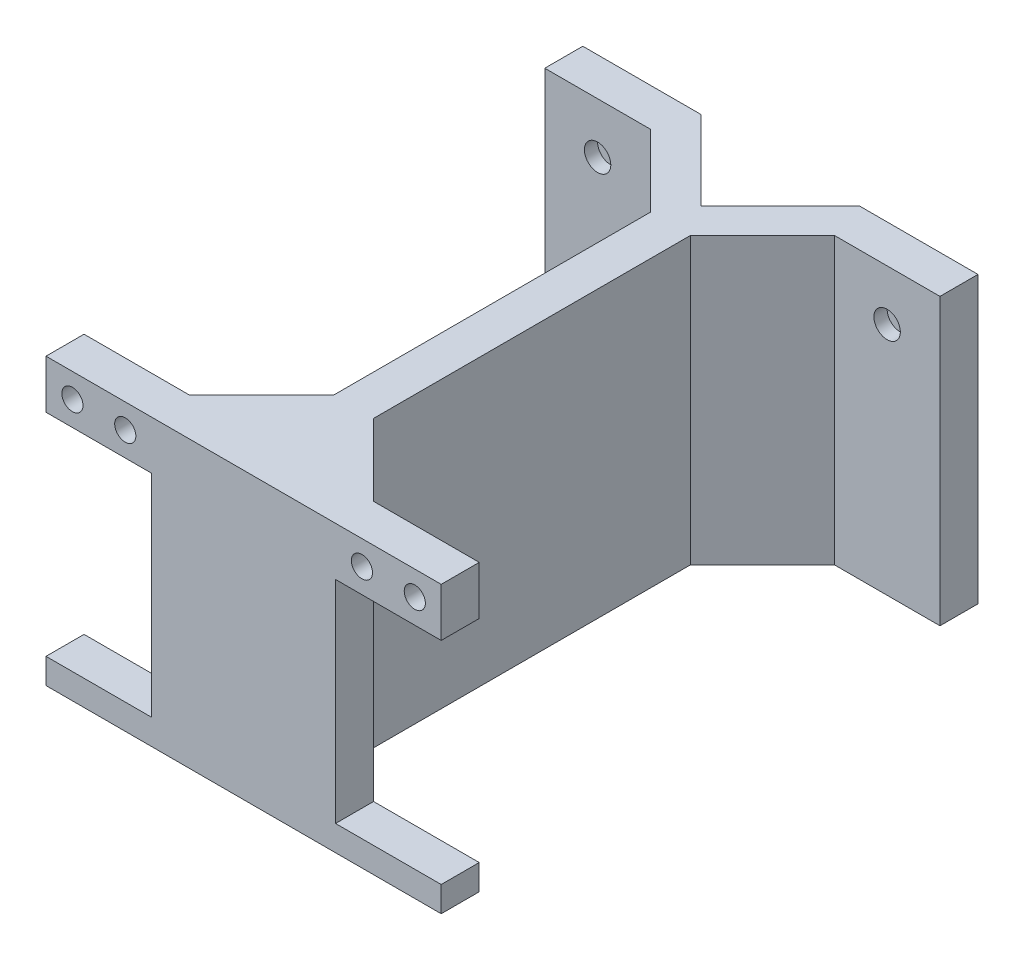
SolidWorks part; units mm, degrees
ref_plane "Front Plane" through (0, 0, 0) normal (0, 0, 1) x (1, 0, 0)
ref_plane "Top Plane" through (0, 0, 0) normal (0, 1, 0) x (1, 0, 0)
ref_plane "Right Plane" through (0, 0, 0) normal (1, 0, 0) x (0, 0, -1)
sketch "Sketch2" plane through (0, 0, 0) normal (0, 0, 1) x (1, 0, 0)
  line L1 (-40.6077, 18.1865) -> (34.1923, 18.1865)
  line L2 (-40.6077, 18.1865) -> (-40.6077, -35.8135)
  line L3 (-40.6077, -35.8135) -> (34.1923, -35.8135)
  line L4 (34.1923, 18.1865) -> (34.1923, -35.8135)
  dimension "D1" = 74.8
  dimension "D2" = 54
extrude "Boss-Extrude1" add sketch "Sketch2" along normal blind 101.6
sketch "Sketch3" plane through (0, 18.1865, 0) normal (0, 1, 0) x (1, 0, 0)
  line L0 (-40.6077, -7.2) -> (-20.6077, -7.2)
  line L1 (-40.6077, -101.6) -> (-40.6077, 0) construction
  line L2 (-20.6077, -7.2) -> (-7.0077, -20.8)
  line L3 (-7.0077, -20.8) -> (-7.0077, -80.8)
  line L4 (-7.0077, -80.8) -> (-20.6077, -94.4)
  line L5 (-20.6077, -94.4) -> (-40.6077, -94.4)
  line L6 (-40.6077, -94.4) -> (-40.6077, -7.2)
  line L7 (34.1923, -101.6) -> (-40.6077, -101.6) construction
  line L8 (34.1923, 0) -> (-40.6077, 0) construction
  dimension "D1" = 7.2
  dimension "D2" = 7.2
  dimension "D3" = 20
  dimension "D4" = 20
  dimension "D5" = 135
  dimension "D6" = 60
extrude "Cut-Extrude1" cut sketch "Sketch3" against normal blind 101.6
sketch "Sketch4" plane through (0, 18.1865, 0) normal (0, 1, 0) x (1, 0, 0)
  line L0 (34.1923, -94.4) -> (14.1923, -94.4)
  line L1 (34.1923, -101.6) -> (34.1923, 0) construction
  line L2 (14.1923, -94.4) -> (0.5923, -80.8)
  line L3 (0.5923, -80.8) -> (0.5923, -20.8)
  line L4 (0.5923, -20.8) -> (14.1923, -7.2)
  line L5 (14.1923, -7.2) -> (34.1923, -7.2)
  line L6 (34.1923, -7.2) -> (34.1923, -94.4)
  line L7 (34.1923, -101.6) -> (-40.6077, -101.6) construction
  line L8 (34.1923, 0) -> (-40.6077, 0) construction
  dimension "D1" = 7.2
  dimension "D2" = 7.2
  dimension "D3" = 20
  dimension "D4" = 20
  dimension "D5" = 135
  dimension "D6" = 135
  dimension "D7" = 60
extrude "Cut-Extrude2" cut sketch "Sketch4" against normal blind 101.6
sketch "Sketch5" plane through (0, 0, 101.6) normal (0, 0, 1) x (1, 0, 0)
  line L0 (34.1923, -35.8135) -> (34.1923, 18.1865) construction
  line L1 (34.1923, -31.0135) -> (14.1923, -31.0135)
  line L2 (34.1923, -31.0135) -> (34.1923, 8.9865)
  line L3 (34.1923, 8.9865) -> (14.1923, 8.9865)
  line L4 (14.1923, -31.0135) -> (14.1923, 8.9865)
  line L5 (-40.6077, -35.8135) -> (34.1923, -35.8135) construction
  dimension "D1" = 4.8
  dimension "D2" = 40
  dimension "D3" = 20
extrude "Cut-Extrude3" cut sketch "Sketch5" against normal blind 10
sketch "Sketch6" plane through (0, 0, 101.6) normal (0, 0, 1) x (1, 0, 0)
  line L0 (-40.6077, 18.1865) -> (-40.6077, -35.8135) construction
  line L1 (-40.6077, 8.9865) -> (-20.6077, 8.9865)
  line L2 (-40.6077, 8.9865) -> (-40.6077, -31.0135)
  line L3 (-40.6077, -31.0135) -> (-20.6077, -31.0135)
  line L4 (-20.6077, 8.9865) -> (-20.6077, -31.0135)
  line L6 (-40.6077, -35.8135) -> (-20.6077, -35.8135) construction
  dimension "D1" = 20
  dimension "D2" = 40
  dimension "D3" = 4.8
extrude "Cut-Extrude4" cut sketch "Sketch6" against normal blind 10
sketch "Sketch7" plane through (0, 0, 7.2) normal (0, 0, 1) x (1, 0, 0)
  line L0 (34.1923, 18.1865) -> (14.1923, 18.1865) construction
  line L1 (14.1923, -35.8135) -> (14.1923, 18.1865) construction
  circle A0 centre (24.1923, 8.5865) radius 2.5
  dimension "D1" = 9.6
  dimension "D2" = 10
extrude "Cut-Extrude5" cut sketch "Sketch7" against normal blind 2.5
sketch "Sketch8" plane through (0, 0, 7.2) normal (0, 0, 1) x (1, 0, 0)
  line L0 (-20.6077, 18.1865) -> (-40.6077, 18.1865) construction
  line L1 (-40.6077, -35.8135) -> (-40.6077, 18.1865) construction
  circle A0 centre (-30.6077, 8.5865) radius 2.5
  dimension "D1" = 9.6
  dimension "D2" = 10
extrude "Cut-Extrude6" cut sketch "Sketch8" against normal blind 2.5 contours A0
sketch "Sketch9" plane through (0, 18.1865, 0) normal (0, 1, 0) x (1, 0, 0)
  line L0 (-18.2482, 0) -> (-3.2077, -15.0405)
  line L1 (34.1923, 0) -> (-40.6077, 0) construction
  line L2 (-3.2077, -15.0405) -> (11.8328, 0)
  line L3 (11.8328, 0) -> (-18.2482, 0)
  line L4 (-7.0077, -20.8) -> (-20.6077, -7.2) construction
  line L5 (14.1923, -7.2) -> (0.5923, -20.8) construction
  line L6 (-40.6077, -7.2) -> (-40.6077, 0) construction
  point P13 (-40.8077, -1.9607)
  dimension "D1" = 37.4
extrude "Cut-Extrude7" cut sketch "Sketch9" against normal through all
sketch "Sketch10" plane through (0, 0, 94.4) normal (0, 0, -1) x (-1, 0, 0)
  line L0 (-34.1923, 8.9865) -> (-34.1923, 18.1865) construction
  line L2 (-34.1923, 8.9865) -> (-14.1923, 8.9865) construction
  circle A0 centre (-29.1923, 13.5865) radius 2
  dimension "D1" = 5
  dimension "D2" = 4.6
extrude "Cut-Extrude8" cut sketch "Sketch10" against normal blind 10
sketch "Sketch12" plane through (0, 0, 94.4) normal (0, 0, -1) x (-1, 0, 0)
  line L1 (-34.1923, 8.9865) -> (-14.1923, 8.9865) construction
  circle A0 centre (-19.1923, 13.5865) radius 2
  point P6 (-321.0428, 42.0673)
  dimension "D1" = 4.6
extrude "Cut-Extrude9" cut sketch "Sketch12" against normal blind 10
sketch "Sketch13" plane through (0, 0, 94.4) normal (0, 0, -1) x (-1, 0, 0)
  line L0 (40.6077, 8.9865) -> (40.6077, 18.1865) construction
  line L1 (20.6077, 8.9865) -> (40.6077, 8.9865) construction
  circle A0 centre (35.6077, 13.5865) radius 2
  circle A1 centre (25.6077, 13.5865) radius 2
  dimension "D1" = 5
  dimension "D3" = 10
  dimension "D2" = 4.6
  dimension "D4" = 4.6
extrude "Cut-Extrude10" cut sketch "Sketch13" against normal blind 10
